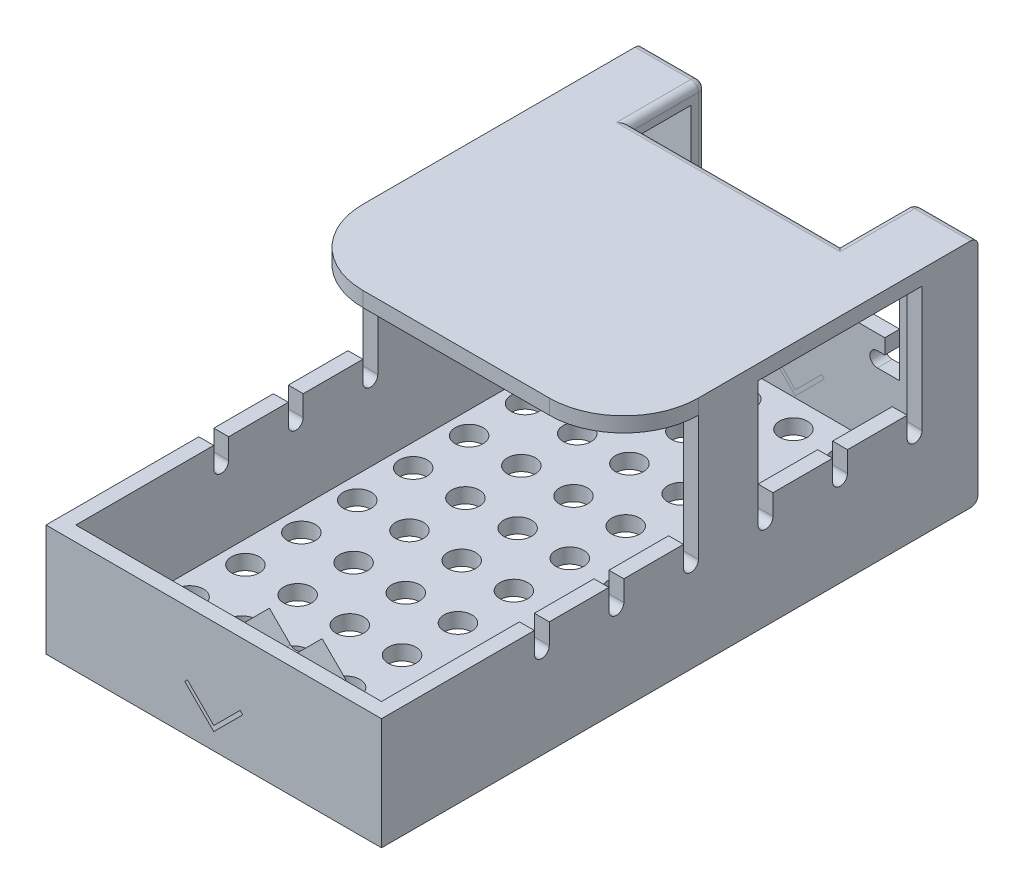
SolidWorks part; units mm, degrees
material "ABS"
ref_plane "Front Plane" through (0, 0, 0) normal (0, 0, 1) x (1, 0, 0)
ref_plane "Top Plane" through (0, 0, 0) normal (0, 1, 0) x (1, 0, 0)
ref_plane "Right Plane" through (0, 0, 0) normal (1, 0, 0) x (0, 0, -1)
sketch "Sketch1" plane through (0, 0, 0) normal (0, 0, 1) x (1, 0, 0)
  line L0 (0, 7.5111) -> (-8.9803, 16.4913)
  line L1 (-57.15, 0) -> (57.15, 0)
  line L2 (-57.15, 0) -> (-57.15, 38.1)
  line L3 (-57.15, 38.1) -> (57.15, 38.1)
  line L4 (57.15, 0) -> (57.15, 38.1)
  line L5 (-8.9803, 16.4913) -> (-9.8783, 15.5933)
  line L6 (-9.8783, 15.5933) -> (0, 5.715)
  line L7 (0, 5.715) -> (9.8783, 15.5933)
  line L8 (9.8783, 15.5933) -> (8.9803, 16.4913)
  line L9 (8.9803, 16.4913) -> (0, 7.5111)
  point P15 (0, 0)
  dimension "D1" = 12.7
  dimension "D2" = 1.27
  dimension "D3" = 5.715
  dimension "D4" = 45
  dimension "D5" = 114.3
  dimension "D6" = 38.1
extrude "Boss-Extrude1" add sketch "Sketch1" against normal blind 203.2
shell "Shell1" thickness 5.08 removed face at (0, 38.1, -101.6)
sketch "Sketch3" plane through (0, 0, 0) normal (1, 0, 0) x (0, 0, -1)
  line L0 (203.2, 38.1) -> (0, 38.1) construction
  line L1 (198.12, 38.1) -> (27.94, 38.1)
  line L2 (198.12, 38.1) -> (198.12, 5.08)
  line L3 (198.12, 5.08) -> (27.94, 5.08)
  line L4 (27.94, 38.1) -> (27.94, 5.08)
  line L5 (203.2, 0) -> (0, 0) construction
  line L6 (0, 0) -> (0, 38.1) construction
  line L7 (203.2, 0) -> (203.2, 38.1) construction
  dimension "D1" = 5.08
  dimension "D2" = 27.94
  dimension "D3" = 5.08
extrude "Cut-Extrude1" cut sketch "Sketch3" against normal up to next and the other way up to next
sketch "Sketch4" plane through (0, 0, -27.94) normal (0, 0, -1) x (-1, 0, 0)
  line L0 (0, 5.715) -> (-9.8783, 15.5933) construction
  line L11 (-9.8783, 15.5933) -> (-8.9803, 16.4913) construction
  line L12 (-8.9803, 16.4913) -> (0, 7.5111) construction
  line L13 (9.8783, 15.5933) -> (0, 5.715) construction
  line L14 (0, 7.5111) -> (8.9803, 16.4913) construction
  line L15 (8.9803, 16.4913) -> (9.8783, 15.5933) construction
  line L16 (0, 5.715) -> (-9.8783, 15.5933)
  line L17 (-9.8783, 15.5933) -> (-8.9803, 16.4913)
  line L18 (-8.9803, 16.4913) -> (0, 7.5111)
  line L19 (9.8783, 15.5933) -> (0, 5.715)
  line L20 (0, 7.5111) -> (8.9803, 16.4913)
  line L21 (8.9803, 16.4913) -> (9.8783, 15.5933)
extrude "Boss-Extrude2" add sketch "Sketch4" against normal blind 2.54
sketch "Sketch5" plane through (-57.15, 0, 0) normal (-1, 0, 0) x (0, 0, 1)
  line L0 (-203.2, 38.1) -> (0, 38.1) construction
  line L1 (-184.15, 38.1) -> (-179.07, 38.1)
  line L2 (-184.15, 38.1) -> (-184.15, 31.115)
  line L4 (-179.07, 38.1) -> (-179.07, 31.115)
  line L5 (-203.2, 38.1) -> (-203.2, 0) construction
  line L6 (-153.67, 38.1) -> (-153.67, 31.115)
  line L7 (-158.75, 38.1) -> (-153.67, 38.1)
  line L8 (-158.75, 38.1) -> (-158.75, 31.115)
  line L9 (-128.27, 38.1) -> (-128.27, 31.115)
  line L10 (-133.35, 38.1) -> (-128.27, 38.1)
  line L11 (-133.35, 38.1) -> (-133.35, 31.115)
  line L12 (-102.87, 38.1) -> (-102.87, 31.115)
  line L13 (-107.95, 38.1) -> (-102.87, 38.1)
  line L14 (-107.95, 38.1) -> (-107.95, 31.115)
  line L15 (-77.47, 38.1) -> (-77.47, 31.115)
  line L16 (-82.55, 38.1) -> (-77.47, 38.1)
  line L17 (-82.55, 38.1) -> (-82.55, 31.115)
  line L18 (-52.07, 38.1) -> (-52.07, 31.115)
  line L19 (-57.15, 38.1) -> (-52.07, 38.1)
  line L20 (-57.15, 38.1) -> (-57.15, 31.115)
  arc A0 (-184.15, 31.115) -> (-179.07, 31.115) centre (-181.61, 31.115) ccw
  arc A1 (-158.75, 31.115) -> (-153.67, 31.115) centre (-156.21, 31.115) ccw
  arc A2 (-133.35, 31.115) -> (-128.27, 31.115) centre (-130.81, 31.115) ccw
  arc A3 (-107.95, 31.115) -> (-102.87, 31.115) centre (-105.41, 31.115) ccw
  arc A4 (-82.55, 31.115) -> (-77.47, 31.115) centre (-80.01, 31.115) ccw
  arc A5 (-57.15, 31.115) -> (-52.07, 31.115) centre (-54.61, 31.115) ccw
  point P9 (-181.61, 28.575)
  dimension "D1" = 19.05
  dimension "D2" = 5.08
  dimension "D3" = 9.525
  dimension "D5" = 25.4
  dimension "D4" = 6
extrude "Cut-Extrude2" cut sketch "Sketch5" against normal through all both and the other way through all
sketch "Sketch6" plane through (0, 5.08, 0) normal (0, 1, 0) x (1, 0, 0)
  line L0 (52.07, 198.12) -> (-52.07, 198.12) construction
  line L1 (-52.07, 198.12) -> (-52.07, 5.08) construction
  circle A0 centre (-44.45, 188.595) radius 4.7625
  circle A1 centre (-26.67, 188.595) radius 4.7625
  circle A2 centre (-8.89, 188.595) radius 4.7625
  circle A3 centre (8.89, 188.595) radius 4.7625
  circle A4 centre (26.67, 188.595) radius 4.7625
  circle A5 centre (44.45, 188.595) radius 4.7625
  circle A6 centre (-26.67, 169.545) radius 4.7625
  circle A7 centre (-8.89, 169.545) radius 4.7625
  circle A8 centre (8.89, 169.545) radius 4.7625
  circle A9 centre (26.67, 169.545) radius 4.7625
  circle A10 centre (44.45, 169.545) radius 4.7625
  circle A11 centre (-26.67, 150.495) radius 4.7625
  circle A12 centre (-8.89, 150.495) radius 4.7625
  circle A13 centre (8.89, 150.495) radius 4.7625
  circle A14 centre (26.67, 150.495) radius 4.7625
  circle A15 centre (44.45, 150.495) radius 4.7625
  circle A16 centre (-26.67, 131.445) radius 4.7625
  circle A17 centre (-8.89, 131.445) radius 4.7625
  circle A18 centre (8.89, 131.445) radius 4.7625
  circle A19 centre (26.67, 131.445) radius 4.7625
  circle A20 centre (44.45, 131.445) radius 4.7625
  circle A21 centre (-26.67, 112.395) radius 4.7625
  circle A22 centre (-8.89, 112.395) radius 4.7625
  circle A23 centre (8.89, 112.395) radius 4.7625
  circle A24 centre (26.67, 112.395) radius 4.7625
  circle A25 centre (44.45, 112.395) radius 4.7625
  circle A26 centre (-26.67, 93.345) radius 4.7625
  circle A27 centre (-8.89, 93.345) radius 4.7625
  circle A28 centre (8.89, 93.345) radius 4.7625
  circle A29 centre (26.67, 93.345) radius 4.7625
  circle A30 centre (44.45, 93.345) radius 4.7625
  circle A31 centre (-26.67, 74.295) radius 4.7625
  circle A32 centre (-8.89, 74.295) radius 4.7625
  circle A33 centre (8.89, 74.295) radius 4.7625
  circle A34 centre (26.67, 74.295) radius 4.7625
  circle A35 centre (44.45, 74.295) radius 4.7625
  circle A36 centre (-26.67, 55.245) radius 4.7625
  circle A37 centre (-8.89, 55.245) radius 4.7625
  circle A38 centre (8.89, 55.245) radius 4.7625
  circle A39 centre (26.67, 55.245) radius 4.7625
  circle A40 centre (44.45, 55.245) radius 4.7625
  circle A41 centre (-26.67, 36.195) radius 4.7625
  circle A42 centre (-8.89, 36.195) radius 4.7625
  circle A43 centre (8.89, 36.195) radius 4.7625
  circle A44 centre (26.67, 36.195) radius 4.7625
  circle A45 centre (44.45, 36.195) radius 4.7625
  circle A46 centre (-44.45, 169.545) radius 4.7625
  circle A47 centre (-44.45, 150.495) radius 4.7625
  circle A48 centre (-44.45, 131.445) radius 4.7625
  circle A49 centre (-44.45, 112.395) radius 4.7625
  circle A50 centre (-44.45, 93.345) radius 4.7625
  circle A51 centre (-44.45, 74.295) radius 4.7625
  circle A52 centre (-44.45, 55.245) radius 4.7625
  circle A53 centre (-44.45, 36.195) radius 4.7625
  dimension "D3" = 9.525
  dimension "D1" = 9.525
  dimension "D2" = 7.62
  dimension "D4" = 6
  dimension "D5" = 9
extrude "Cut-Extrude3" cut sketch "Sketch6" against normal through all both and the other way through all
fillet "Fillet1" radius 2.54 3 edges at (0, 14.6953, -16.51) (6.5492, 5.08, -16.51) (-6.5492, 5.08, -16.51)
sketch "Sketch7" plane through (0, 0, -203.2) normal (0, 0, -1) x (-1, 0, 0)
  line L6 (-8.9803, 16.4913) -> (0, 7.5111) construction
  line L7 (-9.8783, 15.5933) -> (-8.9803, 16.4913) construction
  line L8 (0, 5.715) -> (-9.8783, 15.5933) construction
  line L9 (9.8783, 15.5933) -> (0, 5.715) construction
  line L10 (8.9803, 16.4913) -> (9.8783, 15.5933) construction
  line L11 (0, 7.5111) -> (8.9803, 16.4913) construction
  line L12 (-8.9803, 16.4913) -> (0, 7.5111)
  line L13 (-9.8783, 15.5933) -> (-8.9803, 16.4913)
  line L14 (0, 5.715) -> (-9.8783, 15.5933)
  line L15 (9.8783, 15.5933) -> (0, 5.715)
  line L16 (8.9803, 16.4913) -> (9.8783, 15.5933)
  line L17 (0, 7.5111) -> (8.9803, 16.4913)
extrude "Boss-Extrude3" add sketch "Sketch7" against normal up to surface (5.08 mm away) separate body
sketch "Sketch8" plane through (0, 0, -203.2) normal (0, 0, -1) x (-1, 0, 0)
  line L0 (-30.48, 38.1) -> (-30.48, 33.02)
  line L1 (-57.15, 38.1) -> (57.15, 38.1) construction
  line L2 (-35.56, 38.1) -> (-35.56, 27.94)
  line L3 (-35.56, 38.1) -> (-30.48, 38.1)
  line L4 (0, 20.955) -> (0, -20.955) construction
  line L8 (-30.48, 33.02) -> (-27.94, 33.02)
  line L9 (-35.56, 27.94) -> (-27.94, 27.94)
  line L10 (30.48, 33.02) -> (27.94, 33.02)
  line L11 (30.48, 38.1) -> (30.48, 33.02)
  line L12 (35.56, 38.1) -> (30.48, 38.1)
  line L13 (35.56, 38.1) -> (35.56, 27.94)
  line L14 (35.56, 27.94) -> (27.94, 27.94)
  arc A2 (-27.94, 33.02) -> (-27.94, 27.94) centre (-27.94, 30.48) cw
  arc A3 (27.94, 33.02) -> (27.94, 27.94) centre (27.94, 30.48) ccw
  dimension "D3" = 10.16
  dimension "D1" = 5.08
  dimension "D2" = 30.48
  dimension "D4" = 2.54
  dimension "D5" = 5.08
extrude "Cut-Extrude4" cut sketch "Sketch8" against normal up to surface (5.08 mm away)
sketch "Sketch10" plane through (0, 38.1, 0) normal (0, 1, 0) x (1, 0, 0)
  line L4 (-52.07, 128.27) -> (-57.15, 128.27)
  line L5 (-57.15, 128.27) -> (-57.15, 107.95)
  line L6 (35.56, 203.2) -> (35.56, 198.12)
  line L7 (35.56, 198.12) -> (52.07, 198.12)
  line L8 (52.07, 198.12) -> (52.07, 184.15)
  line L9 (52.07, 184.15) -> (57.15, 184.15)
  line L10 (57.15, 184.15) -> (57.15, 203.2)
  line L11 (57.15, 203.2) -> (35.56, 203.2)
  line L12 (35.56, 203.2) -> (35.56, 198.12)
  line L13 (35.56, 198.12) -> (52.07, 198.12)
  line L14 (52.07, 198.12) -> (52.07, 184.15)
  line L15 (52.07, 184.15) -> (57.15, 184.15)
  line L16 (57.15, 184.15) -> (57.15, 203.2)
  line L17 (57.15, 203.2) -> (35.56, 203.2)
  line L18 (-35.56, 198.12) -> (-35.56, 203.2)
  line L19 (-35.56, 203.2) -> (-57.15, 203.2)
  line L20 (-57.15, 203.2) -> (-57.15, 184.15)
  line L21 (-57.15, 184.15) -> (-52.07, 184.15)
  line L22 (-52.07, 184.15) -> (-52.07, 198.12)
  line L23 (-52.07, 198.12) -> (-35.56, 198.12)
  line L24 (-35.56, 198.12) -> (-35.56, 203.2)
  line L25 (-35.56, 203.2) -> (-57.15, 203.2)
  line L26 (-57.15, 203.2) -> (-57.15, 184.15)
  line L27 (-57.15, 184.15) -> (-52.07, 184.15)
  line L28 (-52.07, 184.15) -> (-52.07, 198.12)
  line L29 (-52.07, 198.12) -> (-35.56, 198.12)
  line L30 (-57.15, 107.95) -> (-52.07, 107.95)
  line L31 (-52.07, 107.95) -> (-52.07, 128.27)
  line L32 (-52.07, 128.27) -> (-57.15, 128.27)
  line L33 (-57.15, 128.27) -> (-57.15, 107.95)
  line L34 (-57.15, 107.95) -> (-52.07, 107.95)
  line L35 (-52.07, 107.95) -> (-52.07, 128.27)
  line L36 (57.15, 128.27) -> (52.07, 128.27)
  line L37 (52.07, 128.27) -> (52.07, 107.95)
  line L38 (52.07, 107.95) -> (57.15, 107.95)
  line L39 (57.15, 107.95) -> (57.15, 128.27)
  line L40 (57.15, 128.27) -> (52.07, 128.27)
  line L41 (52.07, 128.27) -> (52.07, 107.95)
  line L42 (52.07, 107.95) -> (57.15, 107.95)
  line L43 (57.15, 107.95) -> (57.15, 128.27)
  dimension "D1" = 0
  dimension "D2" = 0
  dimension "D3" = 0
  dimension "D4" = 0
extrude "Boss-Extrude4" add sketch "Sketch10" along normal blind 35.56
sketch "Sketch11" plane through (0, 0, -107.95) normal (0, 0, 1) x (1, 0, 0)
  line L0 (-57.15, 73.66) -> (-57.15, 78.74)
  line L1 (-57.15, 78.74) -> (57.15, 78.74)
  line L2 (57.15, 78.74) -> (57.15, 73.66)
  line L3 (-57.15, 73.66) -> (57.15, 73.66)
  dimension "D1" = 5.08
extrude "Boss-Extrude5" add sketch "Sketch11" against normal blind 95.25 and the other way blind 25.4
fillet "Fillet2" radius 2.54 2 edges at (0, 0, -203.2) (0, 78.74, -203.2)
sketch "Sketch12" plane through (0, 78.74, 0) normal (0, 1, 0) x (1, 0, 0)
  line L0 (0, -43.307) -> (0, 43.307) construction
  line L1 (35.56, 177.8) -> (-35.56, 177.8)
  line L2 (35.56, 177.8) -> (35.56, 203.2)
  line L3 (35.56, 203.2) -> (-35.56, 203.2)
  line L4 (-35.56, 177.8) -> (-35.56, 203.2)
  line L5 (35.56, 177.8) -> (-35.56, 203.2) construction
  line L6 (35.56, 203.2) -> (-35.56, 177.8) construction
  line L7 (-57.15, 203.2) -> (57.15, 203.2) construction
  point P0 (0, 190.5)
  dimension "D1" = 25.4
  dimension "D2" = 71.12
extrude "Cut-Extrude5" cut sketch "Sketch12" against normal up to surface (5.08 mm away) up to face at (0, 73.66, -152.273)
fillet "Fillet3" radius 2.54 7 edges at (-35.56, 52.07, -203.2) (-35.56, 77.9961, -202.4561) (35.56, 52.07, -203.2) (35.56, 77.9961, -202.4561) (-35.56, 78.74, -189.23) (0, 78.74, -177.8) (35.56, 78.74, -189.23)
fillet "Fillet4" radius 25.4 2 edges at (-57.15, 76.2, -82.55) (57.15, 76.2, -82.55)
